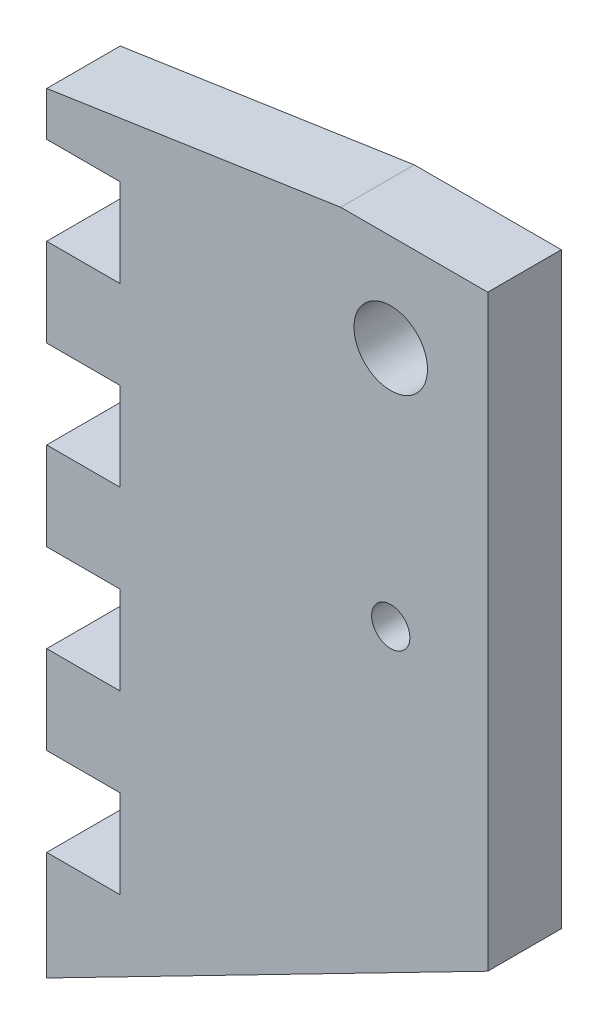
SolidWorks part; units mm, degrees
ref_plane "Front Plane" through (0, 0, 0) normal (0, 0, 1) x (1, 0, 0)
ref_plane "Top Plane" through (0, 0, 0) normal (0, 1, 0) x (1, 0, 0)
ref_plane "Right Plane" through (0, 0, 0) normal (1, 0, 0) x (0, 0, -1)
sketch "Sketch1" plane through (0, 0, 0) normal (0, 0, 1) x (1, 0, 0)
  line L0 (0, 0) -> (-38.1, 0)
  line L1 (0, 0) -> (0, -50.8)
  line L2 (-38.1, 0) -> (-38.1, -7.62)
  line L3 (-38.1, -7.62) -> (-31.75, -7.62)
  line L4 (-31.75, -7.62) -> (-31.75, -15.24)
  line L5 (-31.75, -15.24) -> (-38.1, -15.24)
  line L6 (-38.1, -45.72) -> (-38.1, -70.358)
  line L7 (-38.1, -15.24) -> (-38.1, -22.86)
  line L8 (-38.1, -22.86) -> (-31.75, -22.86)
  line L9 (-31.75, -22.86) -> (-31.75, -30.48)
  line L10 (-31.75, -30.48) -> (-38.1, -30.48)
  line L11 (-38.1, -30.48) -> (-38.1, -38.1)
  line L12 (-38.1, -38.1) -> (-31.75, -38.1)
  line L13 (-31.75, -38.1) -> (-31.75, -45.72)
  line L14 (-31.75, -45.72) -> (-38.1, -45.72)
  line L15 (-38.1, -70.358) -> (0, -50.8)
  circle A0 centre (-8.382, -8.382) radius 3.175
  circle A1 centre (-8.382, -29.21) radius 1.651
  dimension "D9" = 6.35
  dimension "D10" = 3.302
  dimension "D1" = 38.1
  dimension "D2" = 50.8
  dimension "D3" = 7.62
  dimension "D4" = 7.62
  dimension "D5" = 6.35
  dimension "D6" = 6.35
  dimension "D8" = 70.358
  dimension "D11" = 20.828
  dimension "D12" = 8.382
  dimension "D13" = 8.382
  dimension "D14" = 8.382
  dimension "D7" = 3
extrude "Boss-Extrude1" add sketch "Sketch1" along normal blind 6.35 contours L6 L15 L1 L0 L2 L3 L4 L5 L7 L8 L9 L10 L11 L12 L13 L14 A1 A0 region at (-19.2811, -31.1543, 0)
sketch "Sketch2" plane through (0, 0, 0) normal (0, 0, -1) x (-1, 0, 0)
  line L5 (38.1, 0) -> (12.7, 0)
  line L6 (0, 0) -> (38.1, 0) construction
  line L7 (12.7, 0) -> (38.1, -3.81)
  line L8 (38.1, 0) -> (38.1, -7.62) construction
  line L9 (38.1, -3.81) -> (38.1, 0)
  dimension "D1" = 25.4
  dimension "D2" = 3.81
extrude "Cut-Extrude1" cut sketch "Sketch2" against normal blind 8.636
sketch "Sketch4" plane through (0, 0, 6.35) normal (0, 0, 1) x (1, 0, 0)
  line L0 (-38.1, -45.72) -> (-38.1, -53.34)
  line L1 (-38.1, -45.72) -> (-38.1, -70.358) construction
  line L2 (-38.1, -53.34) -> (-31.75, -53.34)
  line L3 (-31.75, -53.34) -> (-31.75, -60.96)
  line L4 (-31.75, -60.96) -> (-38.1, -60.96)
  line L5 (-38.1, -60.96) -> (-38.1, -53.34)
  line M18 (-38.1, -45.72) -> (-38.1, -70.358)
  dimension "D1" = 7.62
  dimension "D2" = 6.35
  dimension "D3" = 6.35
  dimension "D4" = 7.62
extrude "Cut-Extrude2" cut sketch "Sketch4" against normal through all contours L4 L3 L2 M18 region at (-34.925, -57.15, 6.35)
